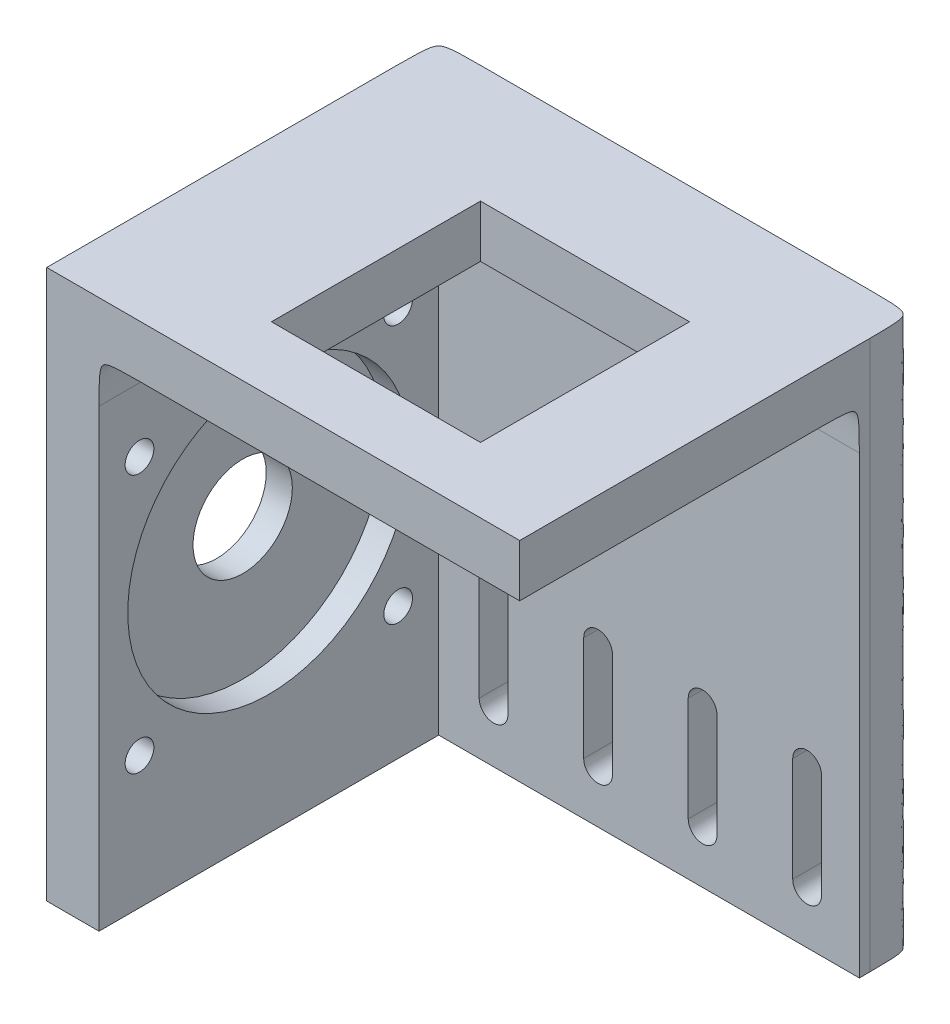
SolidWorks part; units mm, degrees
ref_plane "Front Plane" through (0, 0, 0) normal (0, 0, 1) x (1, 0, 0)
ref_plane "Top Plane" through (0, 0, 0) normal (0, 1, 0) x (1, 0, 0)
ref_plane "Right Plane" through (0, 0, 0) normal (1, 0, 0) x (0, 0, -1)
sketch "Sketch1" plane through (0, 0, 0) normal (0, 1, 0) x (1, 0, 0)
  line L0 (-30.4373, -14.5062) -> (-20.4373, -14.5062)
  line L1 (-20.4373, -14.5062) -> (-20.4373, 50.4938)
  line L2 (-20.4373, 50.4938) -> (60.0627, 50.4938)
  line L3 (60.0627, 50.4938) -> (60.0627, 60.4938)
  line L4 (60.0627, 60.4938) -> (-30.4373, 60.4938)
  line L5 (-30.4373, 60.4938) -> (-30.4373, -14.5062)
  dimension "D1" = 10
  dimension "D2" = 65
  dimension "D3" = 80.5
extrude "Boss-Extrude1" add sketch "Sketch1" along normal blind 95
sketch "Sketch2" plane through (-20.4373, 0, 0) normal (1, 0, 0) x (0, 0, -1)
  line L0 (-14.5062, 95) -> (50.4938, 95) construction
  circle A0 centre (17.9938, 50) radius 27
  point P4 (17.9938, 95)
  dimension "D1" = 54
  dimension "D2" = 45
extrude "Cut-Extrude1" cut sketch "Sketch2" against normal blind 5
sketch "Sketch3" plane through (-20.4373, 0, 0) normal (1, 0, 0) x (0, 0, -1)
  line L0 (17.9938, 50) -> (17.9938, 77) construction
  circle A0 centre (-6.7549, 74.7487) radius 2.75
  circle A1 centre (42.7426, 74.7487) radius 2.75
  circle A2 centre (42.7426, 25.2513) radius 2.75
  circle A3 centre (-6.7549, 25.2513) radius 2.75
  circle A4 centre (17.9938, 50) radius 27 construction
  dimension "D1" = 5.5
  dimension "D2" = 35
  dimension "D3" = 45
  dimension "D4" = 35
  dimension "D5" = 35
extrude "Cut-Extrude2" cut sketch "Sketch3" against normal up to next
sketch "Sketch4" plane through (-25.4373, 0, 0) normal (1, 0, 0) x (0, 0, -1)
  circle A0 centre (17.9938, 50) radius 9.5
  dimension "D1" = 19
extrude "Cut-Extrude3" cut sketch "Sketch4" against normal up to next
sketch "Sketch5" plane through (0, 95, 0) normal (0, 1, 0) x (1, 0, 0)
  line L0 (60.0627, 60.4938) -> (-30.4373, 60.4938) construction
  line L1 (-30.4373, -14.5062) -> (60.0627, -14.5062)
  line L2 (-30.4373, -14.5062) -> (-30.4373, 60.4938)
  line L3 (-30.4373, 60.4938) -> (60.0627, 60.4938)
  line L4 (60.0627, -14.5062) -> (60.0627, 60.4938)
extrude "Boss-Extrude3" add sketch "Sketch5" along normal blind 10
sketch "Sketch6" plane through (0, 95, 0) normal (0, -1, 0) x (1, 0, 0)
  line L0 (60.0627, 14.5062) -> (60.0627, -50.4938) construction
  line L5 (0.0627, 2.0062) -> (40.0627, 2.0062)
  line L6 (0.0627, 2.0062) -> (0.0627, -37.9938)
  line L7 (0.0627, -37.9938) -> (40.0627, -37.9938)
  line L8 (40.0627, 2.0062) -> (40.0627, -37.9938)
  point P10 (60.0627, -17.9938)
  point P11 (40.0627, -17.9938)
  dimension "D1" = 40
  dimension "D2" = 40
  dimension "D3" = 20
extrude "Cut-Extrude4" cut sketch "Sketch6" against normal up to next
sketch "Sketch7" plane through (0, 0, -50.4938) normal (0, 0, 1) x (1, 0, 0)
  line L0 (50.0627, 30) -> (50.0627, 10) construction
  line L1 (52.8127, 30) -> (52.8127, 10)
  line L2 (47.3127, 30) -> (47.3127, 10)
  line L3 (60.0627, 95) -> (60.0627, 0) construction
  line L4 (-20.4373, 0) -> (60.0627, 0) construction
  line L5 (30.0627, 30) -> (30.0627, 10) construction
  line L6 (32.8127, 30) -> (32.8127, 10)
  line L7 (27.3127, 30) -> (27.3127, 10)
  line L8 (10.0627, 30) -> (10.0627, 10) construction
  line L9 (12.8127, 30) -> (12.8127, 10)
  line L10 (7.3127, 30) -> (7.3127, 10)
  line L11 (-9.9373, 30) -> (-9.9373, 10) construction
  line L15 (-7.1873, 30) -> (-7.1873, 10)
  line L16 (-12.6873, 30) -> (-12.6873, 10)
  arc A0 (52.8127, 30) -> (47.3127, 30) centre (50.0627, 30) ccw
  arc A1 (47.3127, 10) -> (52.8127, 10) centre (50.0627, 10) ccw
  arc A2 (32.8127, 30) -> (27.3127, 30) centre (30.0627, 30) ccw
  arc A3 (27.3127, 10) -> (32.8127, 10) centre (30.0627, 10) ccw
  arc A4 (12.8127, 30) -> (7.3127, 30) centre (10.0627, 30) ccw
  arc A5 (7.3127, 10) -> (12.8127, 10) centre (10.0627, 10) ccw
  arc A8 (-7.1873, 30) -> (-12.6873, 30) centre (-9.9373, 30) ccw
  arc A9 (-12.6873, 10) -> (-7.1873, 10) centre (-9.9373, 10) ccw
  point P2 (50.0627, 20)
  point P15 (30.0627, 20)
  point P22 (10.0627, 20)
  point P28 (-9.9373, 20)
  dimension "D2" = 2.75
  dimension "D1" = 20
  dimension "D3" = 10
  dimension "D4" = 20
  dimension "D5" = 4
extrude "Cut-Extrude5" cut sketch "Sketch7" against normal up to next
fillet "Fillet1" radius 8 4 edges at (-30.4373, 52.5, -60.4938) (-20.4373, 95, -17.9938) (19.8127, 95, -50.4938) (60.0627, 52.5, -60.4938) conic rho 0.8
equation "\"D1@Boss-Extrude3\"=\"D1@Sketch1\""
equation "\"D3@Sketch1\"=105.50-25"
